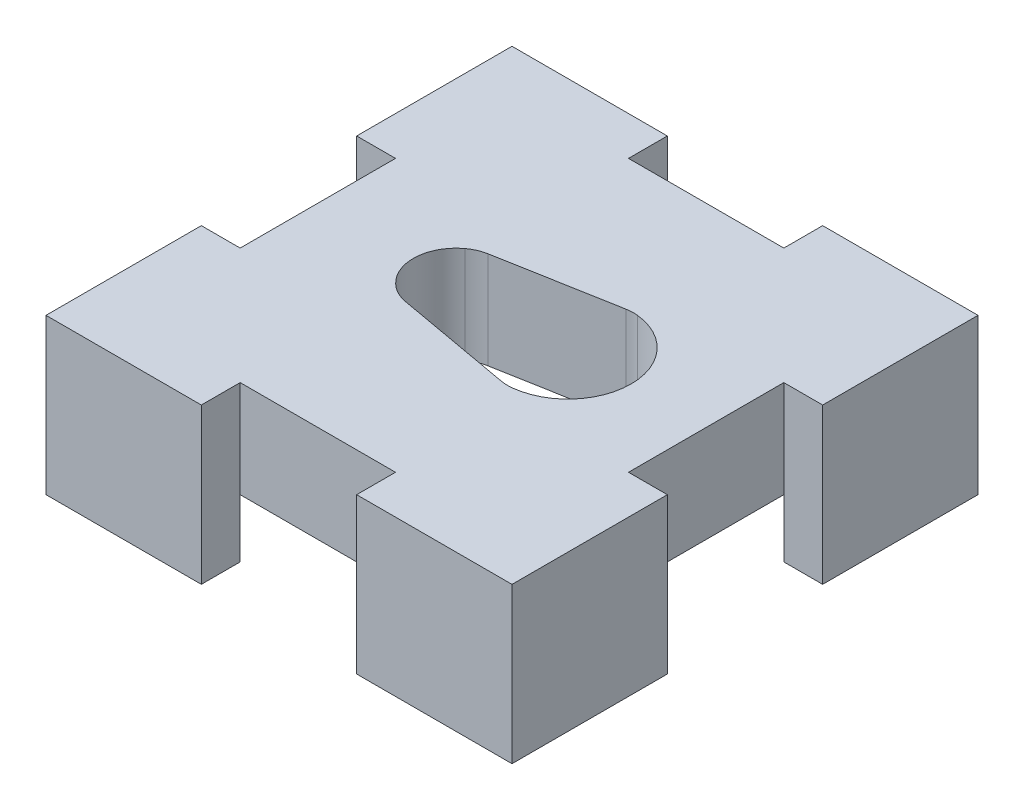
SolidWorks part; units mm, degrees
ref_plane "Front Plane" through (0, 0, 0) normal (0, 0, 1) x (1, 0, 0)
ref_plane "Top Plane" through (0, 0, 0) normal (0, 1, 0) x (1, 0, 0)
ref_plane "Right Plane" through (0, 0, 0) normal (1, 0, 0) x (0, 0, -1)
sketch "Sketch1" plane through (0, 0, 0) normal (0, 1, 0) x (1, 0, 0)
  line L0 (-5, -5) -> (5, -5)
  line L1 (-5, -5) -> (-5, 5)
  line L2 (5, -5) -> (5, 5)
  line L3 (-5, 5) -> (5, 5)
  line L4 (0, -5) -> (0, 5) construction
  line L5 (-1.6772, 1.0648) -> (1.3314, 1.6055)
  line L6 (-5, 0) -> (5, 0) construction
  line L7 (-1.6772, -1.0648) -> (1.3314, -1.6055)
  circle A0 centre (-1.75, 0) radius 0.31
  circle A1 centre (0, 0) radius 0.62
  circle A2 centre (1.75, 0) radius 0.31
  arc A3 (-2.0926, -0.8863) -> (-2.0926, 0.8863) centre (-1.4411, 0) cw
  arc A4 (-1.6772, 1.0648) -> (-2.0926, 0.8863) centre (-1.5003, 0.0806) ccw
  arc A5 (-1.6772, -1.0648) -> (-2.0926, -0.8863) centre (-1.5003, -0.0806) cw
  arc A6 (1.6176, -1.6153) -> (1.6176, 1.6153) centre (1.44, 0) ccw
  arc A7 (1.6176, 1.6153) -> (1.3314, 1.6055) centre (1.5083, 0.6213) ccw
  arc A8 (1.6176, -1.6153) -> (1.3314, -1.6055) centre (1.5083, -0.6213) cw
  dimension "D5" = 0.62
  dimension "D9" = 1.24
  dimension "D10" = 0.62
  dimension "D6" = 1.1
  dimension "D8" = 1
  dimension "D11" = 1
  dimension "D12" = 1
  dimension "D13" = 1
  dimension "D2" = 10
  dimension "D3" = 1.75
  dimension "D4" = 1.75
  dimension "D7" = 10
sketch "Sketch2" plane through (0, 0, 0) normal (0, 1, 0) x (1, 0, 0)
  line L0 (-2, 6) -> (-6, 6)
  line L1 (-6, 6) -> (-6, 2)
  line L2 (-6, 2) -> (-5, 2)
  line L3 (-5, 2) -> (-5, 5)
  line L4 (-5, 5) -> (-2, 5)
  line L5 (-2, 5) -> (-2, 6)
  line L6 (2, 6) -> (2, 5)
  line L7 (0, 0) -> (0, -0.6994) construction
  line L8 (2, 5) -> (5, 5)
  line L9 (0, 0) -> (-0.8324, 0) construction
  line L10 (5, 5) -> (5, 2)
  line L11 (5, 2) -> (6, 2)
  line L12 (6, 2) -> (6, 6)
  line L13 (6, 6) -> (2, 6)
  line L14 (5, -2) -> (5, -5)
  line L15 (5, -5) -> (2, -5)
  line L16 (2, -5) -> (2, -6)
  line L17 (2, -6) -> (6, -6)
  line L18 (6, -6) -> (6, -2)
  line L19 (6, -2) -> (5, -2)
  line L20 (-6, -2) -> (-5, -2)
  line L21 (-5, -2) -> (-5, -5)
  line L22 (-5, -5) -> (-2, -5)
  line L23 (-2, -5) -> (-2, -6)
  line L24 (-2, -6) -> (-6, -6)
  line L25 (-6, -6) -> (-6, -2)
  point P15 (-2, 6)
  point P18 (2, 6)
  point P19 (-2, 5)
  point P20 (2, 5)
  point P21 (-2, -6)
  point P22 (-2, -5)
  point P23 (2, -5)
  point P24 (2, -6)
  point P25 (-6, 2)
  point P26 (-6, -2)
  point P27 (-5, 2)
  point P28 (-5, -2)
  point P29 (5, -2)
  point P30 (6, -2)
  point P31 (5, 2)
  point P32 (6, 2)
  point P33 (6, 6)
extrude "Boss-Extrude1" add sketch "Sketch1" along normal blind 2.5 contours L3 L1 L0 L2 A6 A8 L7 A5 A3 A4 L5 A7 region at (-4.8586, 0, 0)
extrude "Boss-Extrude2" add sketch "Sketch2" along normal blind 2.5
extrude "Boss-Extrude3" add sketch "Sketch2<4>" against normal blind 1.5
sketch "Sketch2<4>" plane through (0, 0, 0) normal (0, 1, 0) x (1, 0, 0) same geometry as "Sketch2"
